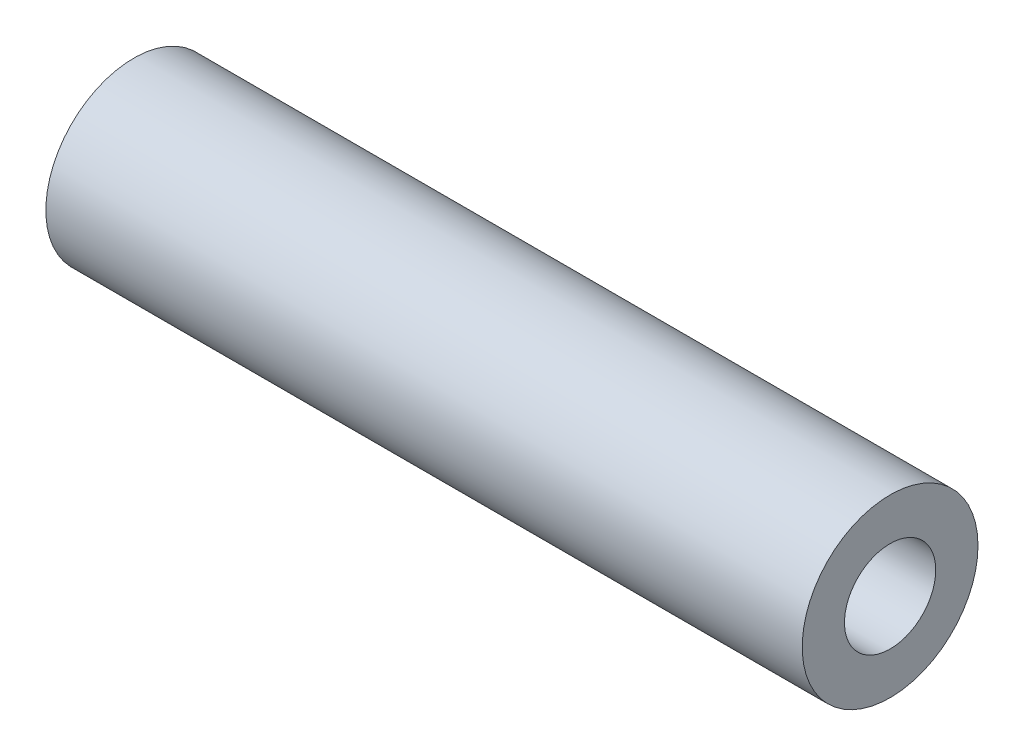
SolidWorks part; units mm, degrees
ref_plane "Front Plane" through (0, 0, 0) normal (0, 0, 1) x (1, 0, 0)
ref_plane "Top Plane" through (0, 0, 0) normal (0, 1, 0) x (1, 0, 0)
ref_plane "Right Plane" through (0, 0, 0) normal (1, 0, 0) x (0, 0, -1)
sketch "Sketch1" plane through (0, 0, 0) normal (1, 0, 0) x (0, 0, -1)
  circle A0 centre (0, 0) radius 42.799
  circle A1 centre (0, 0) radius 22.225
  dimension "D1" = 85.598
  dimension "D2" = 44.45
extrude "Boss-Extrude1" add sketch "Sketch1" along normal blind 368.3
